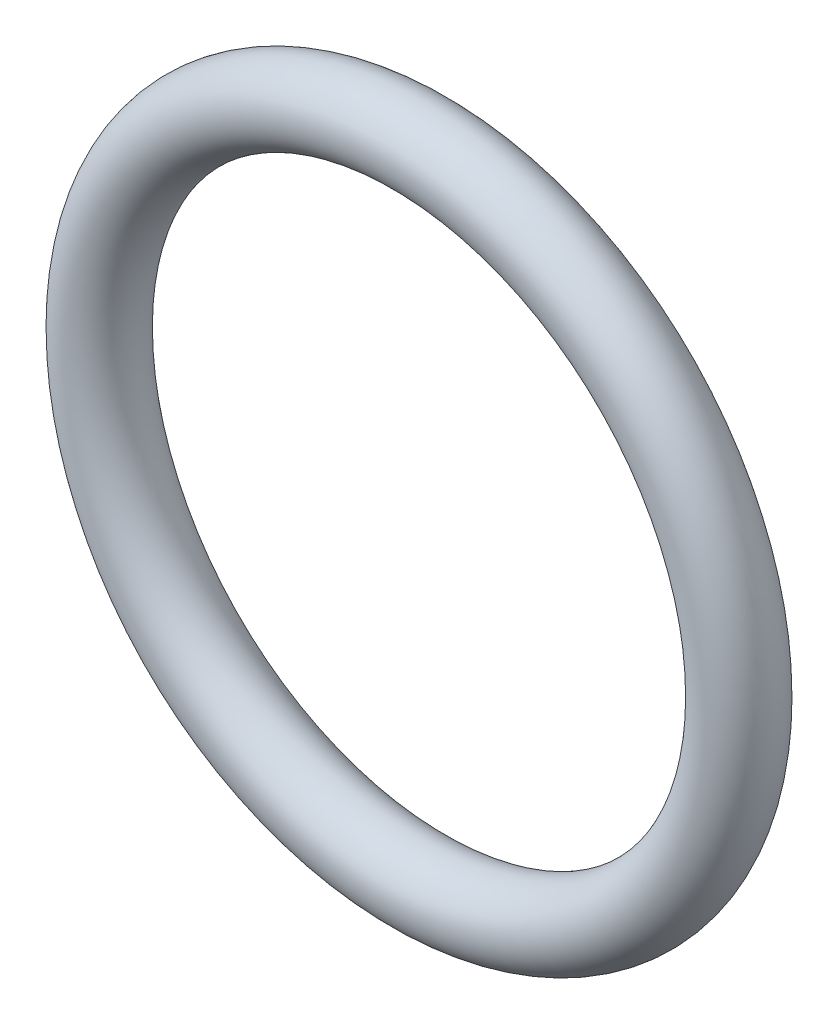
SolidWorks part; units mm, degrees
material "Rubber"
ref_plane "Front Plane" through (0, 0, 0) normal (0, 0, 1) x (1, 0, 0)
ref_plane "Top Plane" through (0, 0, 0) normal (0, 1, 0) x (1, 0, 0)
ref_plane "Right Plane" through (0, 0, 0) normal (1, 0, 0) x (0, 0, -1)
sketch "Sketch1" plane through (0, 0, 0) normal (1, 0, 0) x (0, 0, -1)
  line L0 (-5.0714, 0) -> (5.0573, 0) construction
  circle A0 centre (0, 8.5) radius 1
  dimension "D1" = 2
  dimension "D2" = 8.5
revolve "Revolve1" add sketch "Sketch1" angle 360 about L0
ref_axis "Axis1" through (0, 0, -5.5637) along (0, 0, 1)
